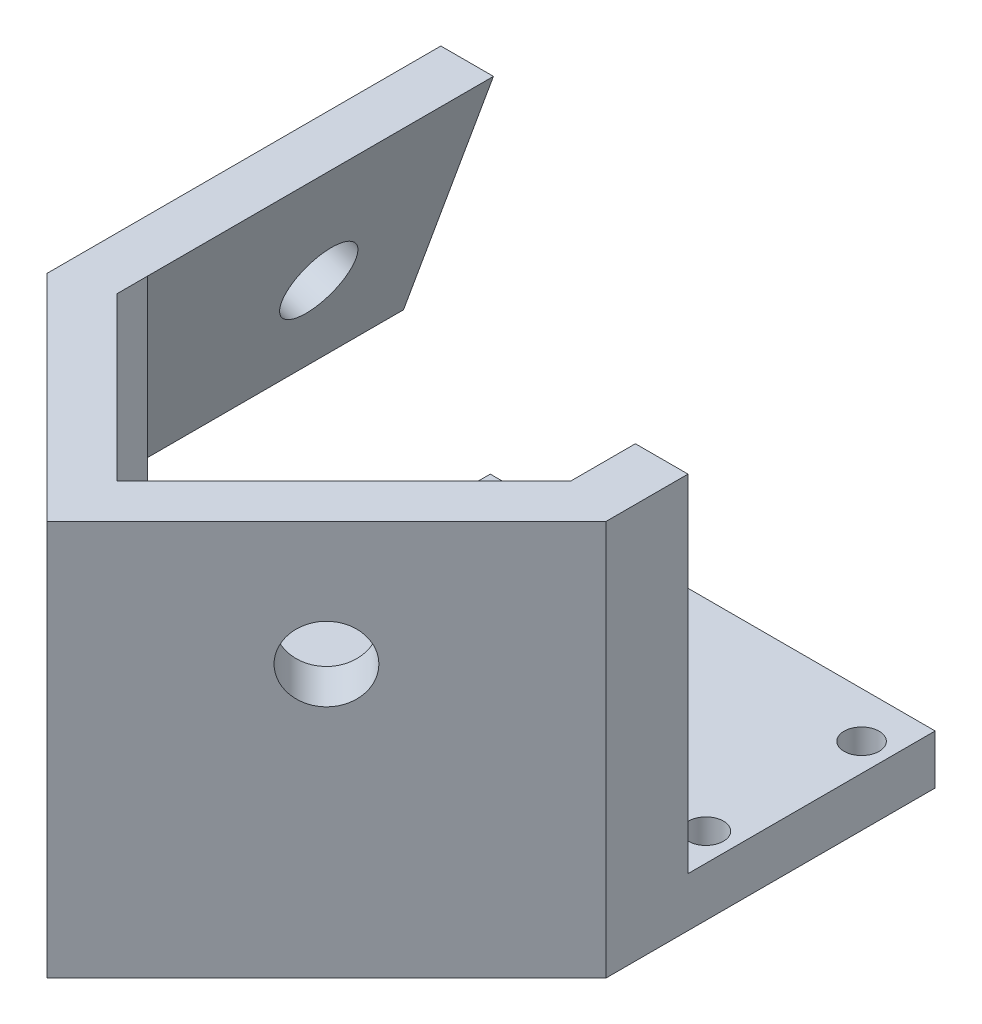
SolidWorks part; units mm, degrees
material "PLA Grey"
ref_plane "Front Plane" through (0, 0, 0) normal (0, 0, 1) x (1, 0, 0)
ref_plane "Top Plane" through (0, 0, 0) normal (0, 1, 0) x (1, 0, 0)
ref_plane "Right Plane" through (0, 0, 0) normal (1, 0, 0) x (0, 0, -1)
sketch "Sketch1" plane through (0, 0, 0) normal (0, 1, 0) x (1, 0, 0)
  line L0 (-35.921, 0) -> (0, 35.921)
  line L1 (-35.921, 0) -> (0, -35.921)
  line L2 (0, 35.921) -> (35.921, 0)
  line L3 (0, -35.921) -> (35.921, 0)
  line L4 (-35.921, 0) -> (35.921, 0) construction
  line L5 (0, 35.921) -> (0, -35.921) construction
  point P1 (0, 0)
  dimension "D1" = 50.8
  dimension "D2" = 50.8
extrude "Boss-Extrude1" add sketch "Sketch1" along normal mid plane 31.75
sketch "Sketch2" plane through (17.9605, 0, 17.9605) normal (0.7071, 0, 0.7071) x (0.7071, 0, -0.7071)
  circle A0 centre (0, 0) radius 4.7625
  dimension "D1" = 9.525
extrude "Cut-Extrude1" cut sketch "Sketch2" against normal blind 8
sketch "Sketch3" plane through (-17.9605, 0, 17.9605) normal (-0.7071, 0, 0.7071) x (0.7071, 0, 0.7071)
  circle A0 centre (0, 0) radius 4.7625
  dimension "D1" = 9.525
extrude "Cut-Extrude2" cut sketch "Sketch3" against normal blind 8
sketch "Sketch4" plane through (0, 15.875, 0) normal (0, 1, 0) x (1, 0, 0)
  line L0 (25.4, 10.521) -> (-25.4, 10.521)
  line L1 (35.921, 0) -> (0, 35.921) construction
  line L2 (0, 35.921) -> (-35.921, 0) construction
  line L3 (-25.4, 10.521) -> (0, 35.921)
  line L4 (0, 35.921) -> (25.4, 10.521)
  dimension "D1" = 25.4
extrude "Cut-Extrude3" cut sketch "Sketch4" against normal through all
sketch "Sketch5" plane through (0, 0, -10.521) normal (0, 0, -1) x (-1, 0, 0)
  line L0 (-35.921, 15.875) -> (-35.921, -15.875)
  line L1 (-35.921, -15.875) -> (39.135, -15.875)
  line L2 (39.135, -15.875) -> (27.579, 15.875)
  line L3 (27.579, 15.875) -> (-35.921, 15.875)
  line L4 (25.4, -15.875) -> (-25.4, -15.875) construction
  line L5 (-35.921, 15.875) -> (-35.921, -15.875) construction
  line L8 (25.4, 15.875) -> (-25.4, 15.875) construction
  point P6 (0, 0)
  dimension "D1" = 70
  dimension "D2" = 63.5
extrude "Boss-Extrude2" add sketch "Sketch5" against normal up to surface and the other way blind 31.75 up to face at (30.6605, 0, -5.2605)
sketch "Sketch6" plane through (-29.455, 10.7207, 0) normal (-0.9397, 0.342, 0) x (0, 0, 1)
  line L0 (-42.271, -28.3026) -> (-42.271, 5.4851) construction
  line L1 (-42.271, -28.3026) -> (-10.521, -28.3026) construction
  circle A0 centre (-26.396, -11.4088) radius 4.7625
  point P4 (-42.271, -11.4088)
  point P7 (-26.396, -28.3026)
  dimension "D1" = 9.525
extrude "Cut-Extrude4" cut sketch "Sketch6" against normal through all
sketch "Sketch7" plane through (0, 0, -42.271) normal (0, 0, -1) x (-1, 0, 0)
  line L1 (-35.921, -15.875) -> (39.135, -15.875) construction
  line L3 (20.8214, 15.875) -> (32.3775, -15.875)
  line L4 (-35.921, -15.875) -> (32.3775, -15.875)
  line L5 (39.135, -15.875) -> (27.579, 15.875) construction
  line L6 (27.579, 15.875) -> (-35.921, 15.875) construction
  line L7 (-35.921, -15.875) -> (-35.921, 15.875)
  line L8 (-35.921, 15.875) -> (20.8214, 15.875)
  dimension "D3" = 6.35
extrude "Cut-Extrude5" cut sketch "Sketch7" against normal blind 31.75
sketch "Sketch8" plane through (0, 15.875, 0) normal (0, 1, 0) x (1, 0, 0)
  line L5 (-42.1413, -6.2203) -> (-8.2965, -39.8855)
  line L6 (0, -35.921) -> (0, -57.0039)
  line L13 (0, -57.0039) -> (-46.5861, -10.6651)
  line L14 (-46.5861, -10.6651) -> (-42.1413, -6.2203)
  line L15 (-8.2965, -39.8855) -> (-8.2965, -27.6245)
  line L16 (-35.921, 0) -> (0, -35.921) construction
  line L17 (-8.2965, -27.6245) -> (0, -35.921)
  line L18 (-25.4, 10.521) -> (-35.921, 0) construction
extrude "Boss-Extrude3" [suppressed] add sketch "Sketch8" against normal up to surface (25.4 mm away) up to face at (2.1042, -15.875, 2.9758)
sketch "Sketch9" plane through (0, -15.875, 0) normal (0, -1, 0) x (1, 0, 0)
  line L0 (-25.4, -10.521) -> (-35.921, 0)
  line L1 (-35.921, 0) -> (-46.442, -10.521)
  line L2 (-46.442, -10.521) -> (-25.4, -10.521)
  line L3 (-35.921, 0) -> (0, 35.921) construction
extrude "Boss-Extrude4" add sketch "Sketch9" against normal up to surface (31.75 mm away) up to face at (-9.5866, 15.875, -10.0783)
sketch "Sketch10" plane through (0, 0, -42.271) normal (0, 0, -1) x (-1, 0, 0)
  line L0 (39.135, -15.875) -> (27.579, 15.875) construction
  line L1 (39.135, -15.875) -> (27.579, 15.875)
  line L6 (27.579, 15.875) -> (39.135, -15.875)
  line L7 (39.135, -15.875) -> (46.442, -15.875)
  line L8 (46.442, -15.875) -> (46.442, 15.875)
  line L9 (46.442, 15.875) -> (27.579, 15.875)
  line L10 (27.579, 15.875) -> (39.135, -15.875)
  line L11 (39.135, -15.875) -> (46.442, -15.875)
  line L12 (46.442, -15.875) -> (46.442, 15.875)
  line L13 (46.442, 15.875) -> (27.579, 15.875)
  line M7 (39.135, -15.875) -> (27.579, 15.875)
  dimension "D1" = 0
extrude "Cut-Extrude6" cut sketch "Sketch10" against normal through all contours L12 L13 L11 M7 region at (-39.4743, 2.3367, -42.271)
sketch "Sketch11" plane through (0, -15.875, 0) normal (0, -1, 0) x (1, 0, 0)
  line L3 (-32.3775, -10.521) -> (-39.135, -10.521)
  line L4 (-39.135, -42.271) -> (-39.135, -3.214) construction
  line L5 (-39.135, -10.521) -> (-39.135, -3.214)
  line L10 (0, 35.921) -> (-39.135, -3.214)
  line L11 (-39.135, -3.214) -> (-39.135, -42.271)
  line L12 (-39.135, -42.271) -> (-32.3775, -42.271)
  line L13 (-32.3775, -42.271) -> (-32.3775, -10.521)
  line L21 (-32.3775, -10.521) -> (35.921, -10.521)
  line L22 (35.921, -10.521) -> (35.921, 0)
  line L23 (35.921, 0) -> (0, 35.921)
  line L24 (0, 35.921) -> (-39.135, -3.214)
  line L29 (-32.3775, -10.521) -> (35.921, -10.521)
  line L30 (35.921, -10.521) -> (35.921, 0)
  line L31 (35.921, 0) -> (0, 35.921)
  dimension "D1" = 0
extrude "Boss-Extrude5" add sketch "Sketch11" along normal blind 12.7
sketch "Sketch12" plane through (0, -28.575, 0) normal (0, -1, 0) x (1, 0, 0)
  line L0 (35.921, -10.521) -> (35.921, 0)
  line L1 (35.921, 0) -> (0, 35.921)
  line L2 (0, 35.921) -> (-39.135, -3.214)
  line L3 (-39.135, -3.214) -> (-39.135, -42.271)
  line L4 (-39.135, -42.271) -> (35.921, -42.271)
  line L5 (35.921, -42.271) -> (35.921, -10.521)
extrude "Boss-Extrude6" add sketch "Sketch12" along normal blind 6.35
sketch "Sketch14" plane through (0, 0, -10.521) normal (0, 0, -1) x (-1, 0, 0)
  line L0 (36.9999, -28.575) -> (20.8214, 15.875)
  line L1 (39.135, -34.925) -> (21.229, -34.925)
  line L2 (20.8214, 15.875) -> (5.0505, 15.875)
  line L3 (21.229, -28.575) -> (5.0505, 15.875)
  line L4 (20.8214, 15.875) -> (-35.921, 15.875) construction
  line L5 (32.3775, -15.875) -> (20.8214, 15.875) construction
  line L6 (39.135, -34.925) -> (-35.921, -34.925) construction
  line L7 (39.135, -34.925) -> (39.135, -28.575)
  line L8 (39.135, -28.575) -> (36.9999, -28.575)
  line L9 (21.229, -28.575) -> (21.229, -34.925)
  line L11 (39.135, -28.575) -> (-35.921, -28.575) construction
  line L12 (-35.921, -34.925) -> (-35.921, -28.575) construction
  dimension "D1" = 57.15
extrude "Cut-Extrude7" cut sketch "Sketch14" along normal through all
sketch "Sketch15" plane through (0, -34.925, 0) normal (0, -1, 0) x (1, 0, 0)
  line L0 (-21.229, -42.271) -> (35.921, -42.271) construction
  line L1 (32.346, -16.396) -> (-17.654, -16.396) construction
  line L2 (32.346, -16.396) -> (32.346, -36.396) construction
  line L3 (32.346, -36.396) -> (-17.654, -36.396) construction
  line L4 (-17.654, -16.396) -> (-17.654, -36.396) construction
  line L5 (32.346, -16.396) -> (-17.654, -36.396) construction
  line L6 (32.346, -36.396) -> (-17.654, -16.396) construction
  line L9 (-21.229, -42.271) -> (-21.229, -10.521) construction
  circle A0 centre (32.346, -36.396) radius 2.25
  circle A1 centre (32.346, -16.396) radius 2.25
  circle A2 centre (-17.654, -16.396) radius 2.25
  circle A3 centre (-17.654, -36.396) radius 2.25
  point P0 (7.346, -26.396)
  point P11 (7.346, -42.271)
  point P14 (-21.229, -26.396)
  dimension "D1" = 4.5
  dimension "D2" = 50
  dimension "D3" = 20
extrude "Cut-Extrude8" cut sketch "Sketch15" against normal up to next
sketch "Sketch17" plane through (0, 15.875, 0) normal (0, 1, 0) x (1, 0, 0)
  line L0 (-20.8214, 10.521) -> (-20.8214, -6.1193)
  line L1 (-20.8214, -6.1193) -> (0, -26.9408)
  line L2 (0, -26.9408) -> (29.1635, 2.2227)
  line L3 (29.1635, 2.2227) -> (29.1635, 10.521)
  line L4 (-20.8214, 10.521) -> (35.921, 10.521) construction
  line L5 (14.5817, -12.359) -> (19.0719, -16.8491) construction
  line L6 (0, -35.921) -> (35.921, 0) construction
  line L7 (-10.4107, -16.53) -> (-14.9009, -21.0202) construction
  line L8 (-27.579, -8.342) -> (0, -35.921) construction
  line L9 (29.1635, 10.521) -> (35.921, 10.521) construction
  line L10 (-20.8214, 10.521) -> (-27.579, 10.521) construction
  line L11 (-27.579, 42.271) -> (-27.579, -8.342) construction
  line L12 (-20.8214, 10.521) -> (29.1635, 10.521)
  dimension "D1" = 6.35
extrude "Cut-Extrude9" cut sketch "Sketch17" against normal up to surface (44.45 mm away) up to face at (-17.654, -28.575, -34.146)
sketch "Sketch20" plane through (0, 0, -10.521) normal (0, 0, -1) x (-1, 0, 0)
  line L7 (32.3775, -15.875) -> (20.8214, 15.875)
  line L8 (20.8214, 15.875) -> (20.8214, -28.575)
  line L9 (20.8214, -28.575) -> (21.229, -28.575)
  line L10 (21.229, -28.575) -> (21.229, -34.925)
  line L11 (21.229, -34.925) -> (39.135, -34.925)
  line L12 (39.135, -34.925) -> (39.135, -15.875)
  line L13 (39.135, -15.875) -> (32.3775, -15.875)
  line L14 (32.3775, -15.875) -> (20.8214, 15.875)
  line L15 (20.8214, 15.875) -> (20.8214, -28.575)
  line L16 (20.8214, -28.575) -> (21.229, -28.575)
  line L17 (21.229, -28.575) -> (21.229, -34.925)
  line L18 (21.229, -34.925) -> (39.135, -34.925)
  line L19 (39.135, -34.925) -> (39.135, -15.875)
  line L20 (39.135, -15.875) -> (32.3775, -15.875)
  dimension "D1" = 0
extrude "Cut-Extrude10" cut sketch "Sketch20" against normal blind 12.7
sketch "Sketch21" plane through (0, 0, 2.179) normal (0, 0, -1) x (-1, 0, 0)
  line L0 (21.229, -28.575) -> (21.229, -34.925) construction
  line L1 (33.742, -34.925) -> (21.229, -34.925)
  line L2 (33.742, -34.925) -> (33.742, -15.875)
  line L3 (33.742, -15.875) -> (21.229, -15.875)
  line L4 (21.229, -34.925) -> (21.229, -15.875)
  line L5 (33.742, -15.875) -> (32.3775, -15.875) construction
extrude "Cut-Extrude11" cut sketch "Sketch21" against normal through all
